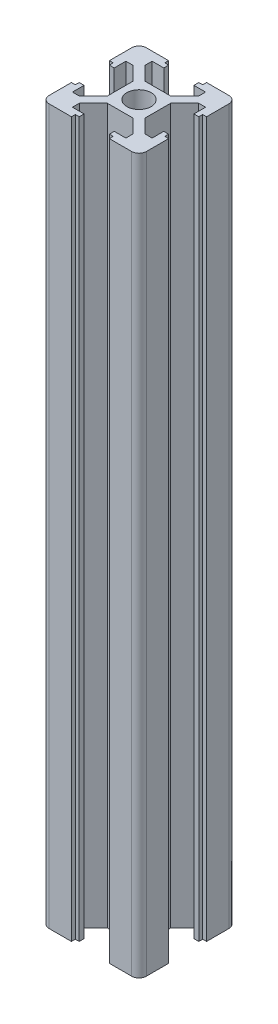
SolidWorks part; units mm, degrees
material "6063-O"
ref_plane "Front Plane" through (0, 0, 0) normal (0, 0, 1) x (1, 0, 0)
ref_plane "Top Plane" through (0, 0, 0) normal (0, 1, 0) x (1, 0, 0)
ref_plane "Right Plane" through (0, 0, 0) normal (1, 0, 0) x (0, 0, -1)
sketch "Sketch1" plane through (0, 0, 0) normal (0, 1, 0) x (1, 0, 0)
  line L0 (0, 14.5399) -> (0, 10) construction
  line L1 (-16.8658, 0) -> (2.5, 0) construction
  line L2 (13.2784, 3.9) -> (3.9, 3.9) construction
  line L3 (0, 0) -> (2.5, 0)
  line L4 (0, 0) -> (0, 2.5)
  line L5 (3.9, 10) -> (8.5, 10)
  line L6 (9.2, 0) -> (16.4291, 0) construction
  line L7 (-2.63, 3.9) -> (2.63, 3.9)
  line L9 (2.5491, 3.9) -> (2.63, 3.9)
  line L10 (3.9, 0) -> (3.9, 2.63)
  line L11 (13.2784, 3.1) -> (2.5491, 3.1) construction
  line L12 (8.2, 7.5573) -> (8.2, -3.0868) construction
  line L13 (9.2, 7.2593) -> (9.2, -8.1534) construction
  line L14 (10, 3.9) -> (9.2, 3.9)
  line L15 (9.2, 3.9) -> (9.2, 3.1)
  line L16 (9.2, 3.1) -> (8.2, 3.1)
  line L17 (8.2, 3.1) -> (8.2, 5.5)
  line L18 (8.2, 5.5) -> (6.77, 5.5)
  line L19 (6.77, 5.5) -> (3.9, 2.63)
  line L20 (5.0973, 5.5) -> (13.0082, 5.5) construction
  line L21 (3.1, 11.2046) -> (3.1, 2.6994) construction
  line L22 (3.9, 10.7498) -> (3.9, 3.9) construction
  line L23 (5.5, 11.523) -> (5.5, 1.4941) construction
  line L24 (-2.2597, 8.2) -> (6.1545, 8.2) construction
  line L25 (-2.9419, 9.2) -> (5.7225, 9.2) construction
  line L26 (3.9, 10) -> (3.9, 9.2)
  line L27 (3.9, 9.2) -> (3.1, 9.2)
  line L28 (3.1, 9.2) -> (3.1, 8.2)
  line L29 (3.1, 8.2) -> (5.5, 8.2)
  line L30 (5.5, 8.2) -> (5.5, 6.77)
  line L31 (5.5, 6.77) -> (2.63, 3.9)
  line L32 (0, 2.5) -> (0, -14.4122) construction
  line L33 (10, 3.9) -> (10, 8.5)
  line L34 (9.2, 0) -> (10, 0)
  line L35 (2.63, 3.9) -> (2.5491, 3.9) construction
  line L36 (3.9, 2.63) -> (3.9, 2.0627) construction
  line L37 (10, -3.9) -> (10, -8.5)
  line L38 (3.9, -10) -> (8.5, -10)
  line L39 (3.9, -10) -> (3.9, -9.2)
  line L40 (3.9, -9.2) -> (3.1, -9.2)
  line L41 (3.1, -9.2) -> (3.1, -8.2)
  line L42 (3.1, -8.2) -> (5.5, -8.2)
  line L43 (5.5, -8.2) -> (5.5, -6.77)
  line L44 (5.5, -6.77) -> (2.63, -3.9)
  line L45 (0, -3.9) -> (2.63, -3.9)
  line L46 (3.9, 0) -> (3.9, -2.63)
  line L47 (6.77, -5.5) -> (3.9, -2.63)
  line L48 (8.2, -5.5) -> (6.77, -5.5)
  line L49 (8.2, -3.1) -> (8.2, -5.5)
  line L50 (9.2, -3.1) -> (8.2, -3.1)
  line L51 (9.2, -3.9) -> (9.2, -3.1)
  line L52 (10, -3.9) -> (9.2, -3.9)
  line L53 (-3.9, -10) -> (-8.5, -10)
  line L54 (-10, -3.9) -> (-10, -8.5)
  line L55 (-10, -3.9) -> (-9.2, -3.9)
  line L56 (-9.2, -3.9) -> (-9.2, -3.1)
  line L57 (-9.2, -3.1) -> (-8.2, -3.1)
  line L58 (-8.2, -3.1) -> (-8.2, -5.5)
  line L59 (-8.2, -5.5) -> (-6.77, -5.5)
  line L60 (-6.77, -5.5) -> (-3.9, -2.63)
  line L61 (-3.9, 0) -> (-3.9, -2.63)
  line L62 (0, -3.9) -> (-2.63, -3.9)
  line L63 (-5.5, -6.77) -> (-2.63, -3.9)
  line L64 (-5.5, -8.2) -> (-5.5, -6.77)
  line L65 (-3.1, -8.2) -> (-5.5, -8.2)
  line L66 (-3.1, -9.2) -> (-3.1, -8.2)
  line L67 (-3.9, -9.2) -> (-3.1, -9.2)
  line L68 (-3.9, -10) -> (-3.9, -9.2)
  line L69 (-10, 3.9) -> (-10, 8.5)
  line L70 (-3.9, 10) -> (-8.5, 10)
  line L71 (-3.9, 10) -> (-3.9, 9.2)
  line L72 (-3.9, 9.2) -> (-3.1, 9.2)
  line L73 (-3.1, 9.2) -> (-3.1, 8.2)
  line L74 (-3.1, 8.2) -> (-5.5, 8.2)
  line L75 (-5.5, 8.2) -> (-5.5, 6.77)
  line L76 (-5.5, 6.77) -> (-2.63, 3.9)
  line L78 (-3.9, 0) -> (-3.9, 2.63)
  line L79 (-6.77, 5.5) -> (-3.9, 2.63)
  line L80 (-8.2, 5.5) -> (-6.77, 5.5)
  line L81 (-8.2, 3.1) -> (-8.2, 5.5)
  line L82 (-9.2, 3.1) -> (-8.2, 3.1)
  line L83 (-9.2, 3.9) -> (-9.2, 3.1)
  line L84 (-10, 3.9) -> (-9.2, 3.9)
  line L85 (0, 3.9) -> (-2.63, 3.9) [skipped]
  circle A0 centre (0, 0) radius 2.5
  arc A1 (8.5, 10) -> (10, 8.5) centre (8.5, 8.5) cw
  arc A2 (10, -8.5) -> (8.5, -10) centre (8.5, -8.5) cw
  arc A4 (-8.5, -10) -> (-10, -8.5) centre (-8.5, -8.5) cw
  arc A6 (-10, 8.5) -> (-8.5, 10) centre (-8.5, 8.5) cw
  point P12 (10, 10)
  point P126 (0, 0)
  dimension "D3" = 5
  dimension "D4" = 1.5
  dimension "D1" = 10
  dimension "D2" = 10
  dimension "D6" = 3.9
  dimension "D7" = 3.9
  dimension "D8" = 3.1
  dimension "D9" = 4
  dimension "D11" = 5.5
  dimension "D12" = 1.8
  dimension "D13" = 0.8
  dimension "D14" = 3.9
  dimension "D15" = 3.1
  dimension "D16" = 5.5
  dimension "D17" = 1.27
  dimension "D18" = 1.27
  dimension "D19" = 1.27
  dimension "D20" = 1.27
extrude "Boss-Extrude1" add sketch "Sketch1" along normal blind 147 contours A6 L69 L84 L83 L82 L81 L80 L79 L78 L61 L60 L59 L58 L57 L56 L55 L54 A4 L53 L68 L67 L66 L65 L64 L63 L62 L45 L44 L43 L42 L41 L40 L39 L38 A2 L37 L52 L51 L50 L49 L48 L47 L46 L10 L19 L18 L17 L16 L15 L14 L33 region at (6.2, 0, -9.7172)
